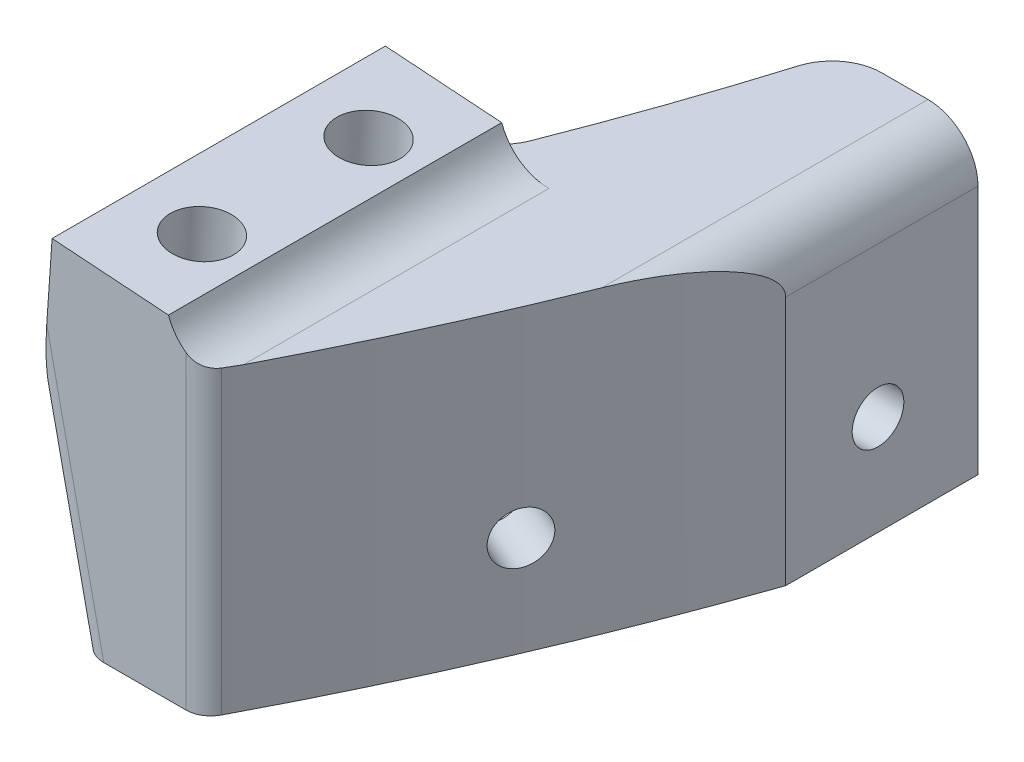
SolidWorks part; units mm, degrees
material "ABS"
ref_plane "Plan de face" through (0, 0, 0) normal (0, 0, 1) x (1, 0, 0)
ref_plane "Plan de dessus" through (0, 0, 0) normal (0, 1, 0) x (1, 0, 0)
ref_plane "Plan de droite" through (0, 0, 0) normal (1, 0, 0) x (0, 0, -1)
sketch "Esquisse1" plane through (0, 0, 0) normal (0, 1, 0) x (1, 0, 0)
  line L0 (142.5, -81) -> (152.866, -81)
  line L1 (163.5, -56.5398) -> (163.5, -45)
  line L2 (163.5, -45) -> (155.5, -45)
  line L4 (149.9475, -61) -> (142.5, -61)
  line L5 (142.5, -61) -> (142.5, -81)
  arc A0 (152.866, -81) -> (163.5, -56.5398) centre (0, 0) ccw
  arc A1 (149.9475, -61) -> (155.5, -45) centre (0, 0) ccw
  dimension "D1" = 346
  dimension "D2" = 163.5
  dimension "D3" = 45
  dimension "D4" = 8
  dimension "D5" = 20
  dimension "D6" = 81
  dimension "D7" = 142.5
extrude "Boss.-Extru.1" add sketch "Esquisse1" along normal blind 12 and the other way blind 6
sketch "Esquisse2" plane through (0, 0, 81) normal (0, 0, 1) x (1, 0, 0)
  line L0 (142.5, -6) -> (142.5, 12)
  line L2 (142.5, 12) -> (143.7587, 12)
  line L3 (143.7587, 12) -> (142.5, -6)
  line L4 (142.5, 12) -> (152.866, 12) construction
  dimension "D1" = 4
extrude "Enlèv. mat.-Extru.1" cut sketch "Esquisse2" against normal through all
sketch "Esquisse3" plane through (0, 0, 81) normal (0, 0, 1) x (1, 0, 0)
  line L0 (143.7587, 12) -> (143.9331, 14.4939)
  line L1 (142.5, -6) -> (143.7587, 12) construction
  line L2 (143.9331, 14.4939) -> (150.916, 14.0056)
  line L3 (150.916, 14.0056) -> (150.916, 12)
  line L4 (143.7587, 12) -> (152.866, 12) construction
  line L5 (150.916, 12) -> (143.7587, 12)
  dimension "D1" = 2.5
  dimension "D2" = 7
extrude "Boss.-Extru.2" add sketch "Esquisse3" against normal up to surface (20 mm away) up to face at (146.5384, 3, 61)
sketch "Esquisse4" plane through (0, 0, 81) normal (0, 0, 1) x (1, 0, 0)
  line L0 (142.5, -6) -> (143.2355, 4.5183)
  line L1 (142.5, -6) -> (143.9331, 14.4939) construction
  line L2 (143.2355, 4.5183) -> (145.5, -6)
  line L3 (142.5, -6) -> (152.866, -6) construction
  line L4 (145.5, -6) -> (142.5, -6)
  line L5 (150.916, 14.0056) -> (143.9331, 14.4939) construction
  dimension "D1" = 3
  dimension "D2" = 10
extrude "Enlèv. mat.-Extru.2" cut sketch "Esquisse4" against normal through all
sketch "Esquisse5" plane through (1.709, 24.4392, 0) normal (0.0698, 0.9976, 0) x (0.9976, -0.0698, 0)
  line L0 (142.5714, -71) -> (149.5714, -71) construction
  line L1 (142.5714, -61) -> (142.5714, -81) construction
  line L2 (149.5714, -61) -> (149.5714, -81) construction
  circle A0 centre (146.5714, -66) radius 1.9
  circle A1 centre (146.5714, -76) radius 1.9
  dimension "D1" = 10
  dimension "D2" = 3.8
  dimension "D3" = 4
extrude "Enlèv. mat.-Extru.3" cut sketch "Esquisse5" against normal blind 10
sketch "Esquisse7" plane through (0, 0, 0) normal (0, 1, 0) x (1, 0, 0)
  line L0 (150.916, -61) -> (150.916, -81) construction
  line L1 (156.5, -52.9) -> (160, -52.9)
  line L2 (150.916, -53.8846) -> (150.916, -51)
  line L3 (150.916, -51) -> (163.5, -51)
  line L4 (163.5, -52.55) -> (163.5, -51)
  line L5 (163.5, -56.5398) -> (163.5, -45) construction
  line L6 (150.916, -51) -> (143.9331, -51) construction
  line L9 (163.5, -52.55) -> (160, -52.55)
  line L10 (160, -52.9) -> (160, -52.55)
  line L11 (143.9331, -61) -> (143.9331, -81) construction
  line L12 (156.5, -52.9) -> (150.916, -53.8846)
  dimension "D1" = 3.1
  dimension "D2" = 3.8
  dimension "D3" = 51
  dimension "D4" = 3.5
  dimension "D5" = 3.5
  dimension "D6" = 10
revolve "Enlèvement de matière-Révolution1" cut sketch "Esquisse7" angle 360 about L6
fillet "Congé1" radius 3 4 edges at (150.916, 12, 71) (163.5, 12, 50.7699) (155.5, 3, 45) (149.9475, 3, 61)
sketch "Esquisse8" plane through (0, 0, 0) normal (0, 1, 0) x (1, 0, 0)
  line L0 (0, 0) -> (143.1528, -61.1935) construction
  line L1 (143.1528, -61.1935) -> (159.0755, -68)
  line L2 (159.0755, -68) -> (159.6847, -66.5748)
  line L3 (159.6847, -66.5748) -> (156.4664, -65.199)
  line L4 (156.4664, -65.199) -> (156.604, -64.8772)
  line L5 (156.604, -64.8772) -> (153.3857, -63.5015)
  line L6 (153.3857, -63.5015) -> (144.6146, -57.7738)
  line L7 (144.6146, -57.7738) -> (143.1528, -61.1935)
  line L8 (-11.1455, 0) -> (11.1455, 0) construction
  arc A0 (153.7464, -79.3161) -> (160.5, -64.5659) centre (0, 0) ccw construction
  dimension "D1" = 3.1
  dimension "D2" = 3.8
  dimension "D3" = 3.5
  dimension "D4" = 10
  dimension "D5" = 3.5
  dimension "D6" = 68
  dimension "D7" = 23.145
revolve "Enlèvement de matière-Révolution2" cut sketch "Esquisse8" angle 360 about L0
fillet "Congé2" radius 1.5 6 edges at (149.1211, 4.1067, 76) (145.3304, 4.3718, 66) (143.3259, 4.0986, 61) (144.3678, -0.7409, 81) (145.2128, -4.6661, 61) (152.866, 3.0661, 81)
